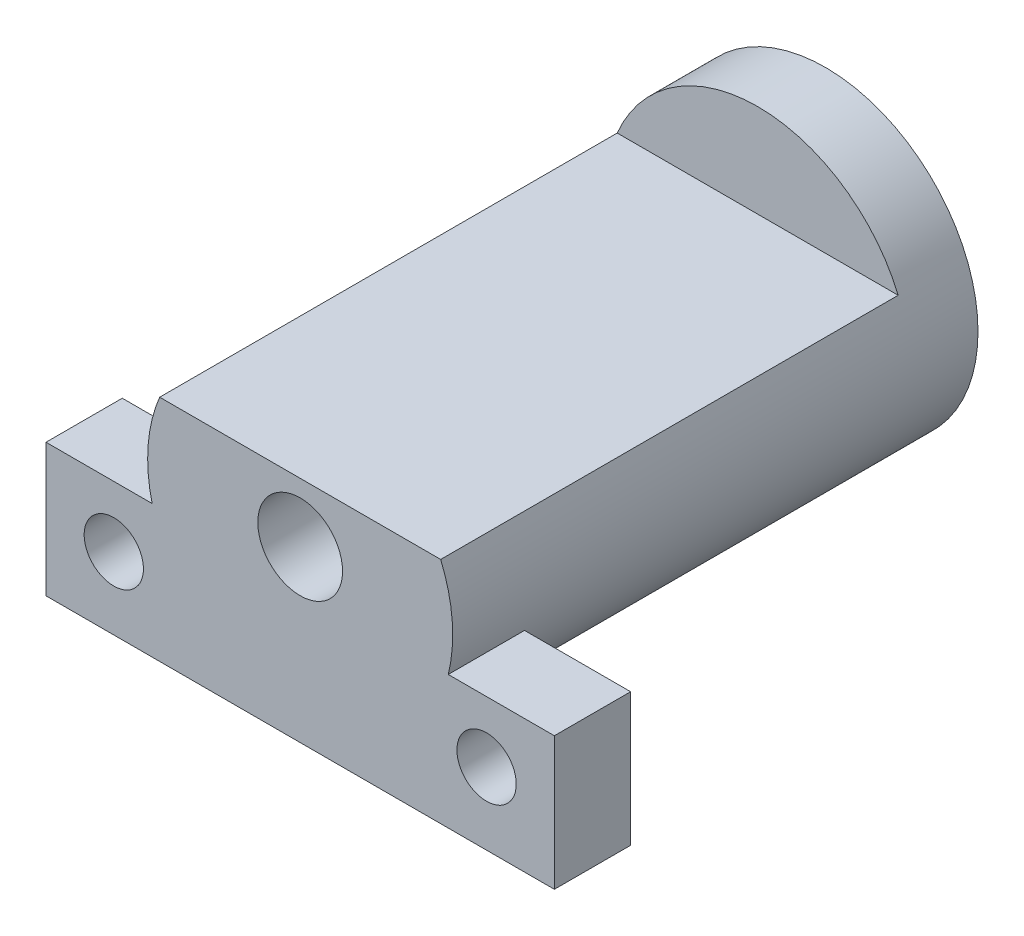
SolidWorks part; units mm, degrees
ref_plane "Front Plane" through (0, 0, 0) normal (0, 0, 1) x (1, 0, 0)
ref_plane "Top Plane" through (0, 0, 0) normal (0, 1, 0) x (1, 0, 0)
ref_plane "Right Plane" through (0, 0, 0) normal (1, 0, 0) x (0, 0, -1)
sketch "Sketch1" plane through (0, 0, 0) normal (0, 0, 1) x (1, 0, 0)
  circle A0 centre (0, 0) radius 18
  dimension "D1" = 36
extrude "Boss-Extrude1" add sketch "Sketch1" along normal blind 62
sketch "Sketch2" plane through (0, 0, 62) normal (0, 0, 1) x (1, 0, 0)
  line L1 (-17.2898, 21.1304) -> (22.2392, 21.1304)
  line L2 (-17.2898, 21.1304) -> (-17.2898, 7)
  line L3 (-17.2898, 7) -> (22.2392, 7)
  line L4 (22.2392, 21.1304) -> (22.2392, 7)
  circle A0 centre (0, 0) radius 18 construction
  dimension "D1" = 7
extrude "Cut-Extrude1" cut sketch "Sketch2" against normal blind 54
sketch "Sketch3" plane through (0, 0, 62) normal (0, 0, 1) x (1, 0, 0)
  line L1 (-30, -4.3129) -> (30, -4.3129)
  line L2 (-30, -4.3129) -> (-30, -20.0129)
  line L3 (-30, -20.0129) -> (30, -20.0129)
  line L4 (30, -4.3129) -> (30, -20.0129)
  arc A0 (-16.5831, 7) -> (16.5831, 7) centre (0, 0) ccw construction
  dimension "D1" = 60
  dimension "D2" = 30
  dimension "D3" = 15.7
extrude "Boss-Extrude2" add sketch "Sketch3" against normal blind 9
sketch "Sketch4" plane through (0, 0, 53) normal (0, 0, -1) x (-1, 0, 0)
  line L0 (30, -20.0129) -> (-30, -20.0129) construction
  line L1 (-30, -20.0129) -> (-30, -4.3129) construction
  circle A0 centre (-22, -11.5129) radius 3.5
  point P4 (0, 0)
  dimension "D3" = 7
  dimension "D1" = 8.5
  dimension "D2" = 8
extrude "Cut-Extrude2" cut sketch "Sketch4" against normal blind 10
pattern_linear "LPattern1" count 2 spacing 44 along (-1, 0, 0) of "Cut-Extrude2"
sketch "Sketch6" plane through (0, 0, 0) normal (0, 0, -1) x (-1, 0, 0)
  circle A0 centre (0, 0) radius 5
  circle A1 centre (0, 0) radius 18 construction
extrude "Cut-Extrude3" cut sketch "Sketch6" against normal blind 100
